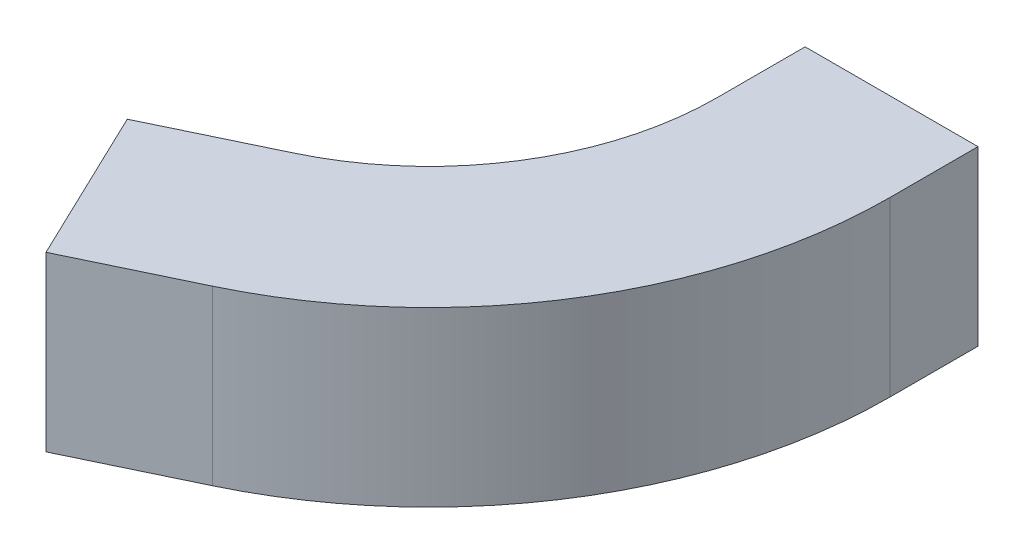
SolidWorks part; units mm, degrees
ref_plane "Front Plane" through (0, 0, 0) normal (0, 0, 1) x (1, 0, 0)
ref_plane "Top Plane" through (0, 0, 0) normal (0, 1, 0) x (1, 0, 0)
ref_plane "Right Plane" through (0, 0, 0) normal (1, 0, 0) x (0, 0, -1)
sketch "Sketch1" plane through (0, 0, 0) normal (0, 1, 0) x (1, 0, 0)
  line L0 (0, 0) -> (40, 0)
  line L1 (0, 0) -> (17.2708, -36.0793)
  line L2 (17.2708, -36.0793) -> (7.5024, -40.7554)
  line L3 (25, 0) -> (40, 0)
  line L4 (25, 0) -> (25, 7.62)
  line L5 (25, 7.62) -> (40, 7.62)
  line L6 (40, 0) -> (40, 7.62)
  line L7 (7.5024, -40.7554) -> (1.0258, -27.2257)
  line L8 (1.0258, -27.2257) -> (10.7943, -22.5496)
  circle A0 centre (0, 0) radius 40
  circle A1 centre (0, 0) radius 25
  dimension "D1" = 15
  dimension "D2" = 80
  dimension "D3" = 64.42
  dimension "D4" = 7.62
  dimension "D5" = 10.83
extrude "Boss-Extrude1" add sketch "Sketch1" along normal blind 15 contours L7 A0 L1 L8 | A1 L1 A0 L0 | L0 A0 L5 L4 | A0 L7 L2 | A0 L6 L5 region at (32.38, 0, -3.7785) region at (26.5354, 0, 16.7167) region at (9.1281, 0, 31.3958) region at (39.7806, 0, -5.7185) region at (9.7424, 0, 39.1879)
